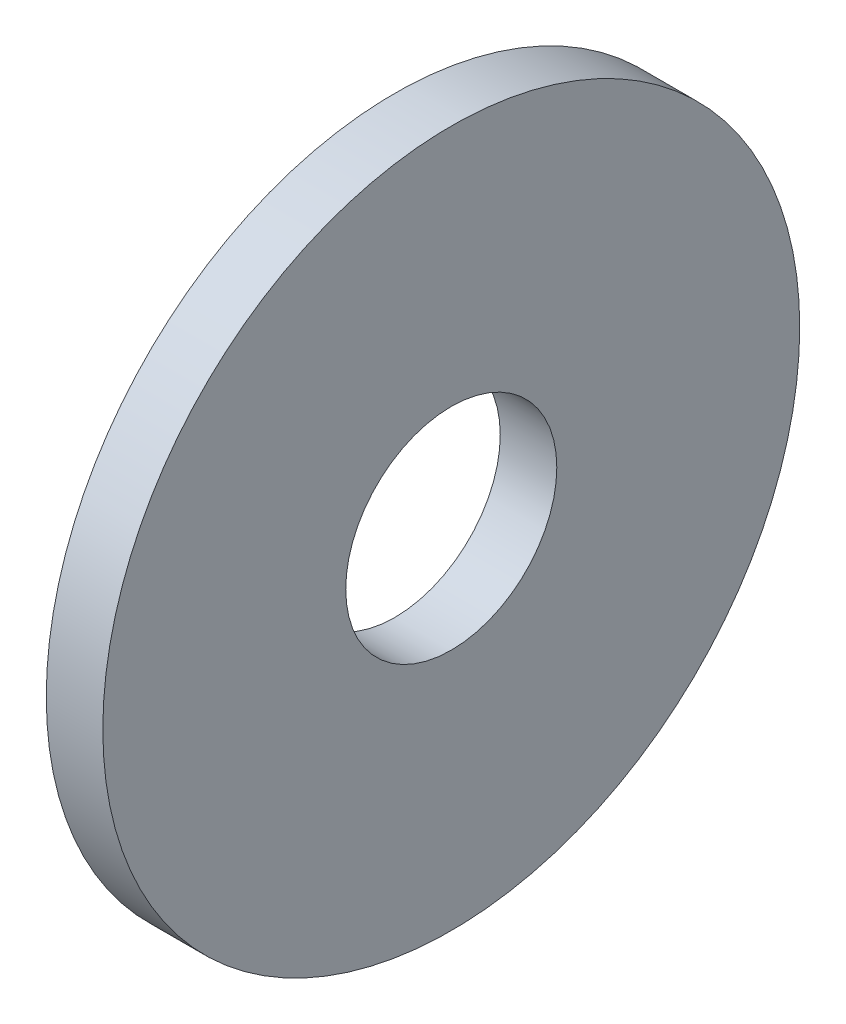
SolidWorks part; units mm, degrees
material "Stainless Steel (ferritic)"
ref_plane "Front Plane" through (0, 0, 0) normal (0, 0, 1) x (1, 0, 0)
ref_plane "Top Plane" through (0, 0, 0) normal (0, 1, 0) x (1, 0, 0)
ref_plane "Right Plane" through (0, 0, 0) normal (1, 0, 0) x (0, 0, -1)
sketch "Sketch1" plane through (0, 0, 0) normal (1, 0, 0) x (0, 0, -1)
  circle A0 centre (0, 0) radius 11.1125
  circle A1 centre (0, 0) radius 3.3655
  dimension "OD" = 22.225
  dimension "ID" = 6.731
extrude "Boss-Extrude1" add sketch "Sketch1" along normal blind 1.8034
ref_axis "Center Axis 1" through (8.8544, 0, 0) along (-1, 0, 0)
ref_plane "Contact Plane 1" through (0, 0, 0) normal (-1, 0, 0) x (0, 0, 1)
